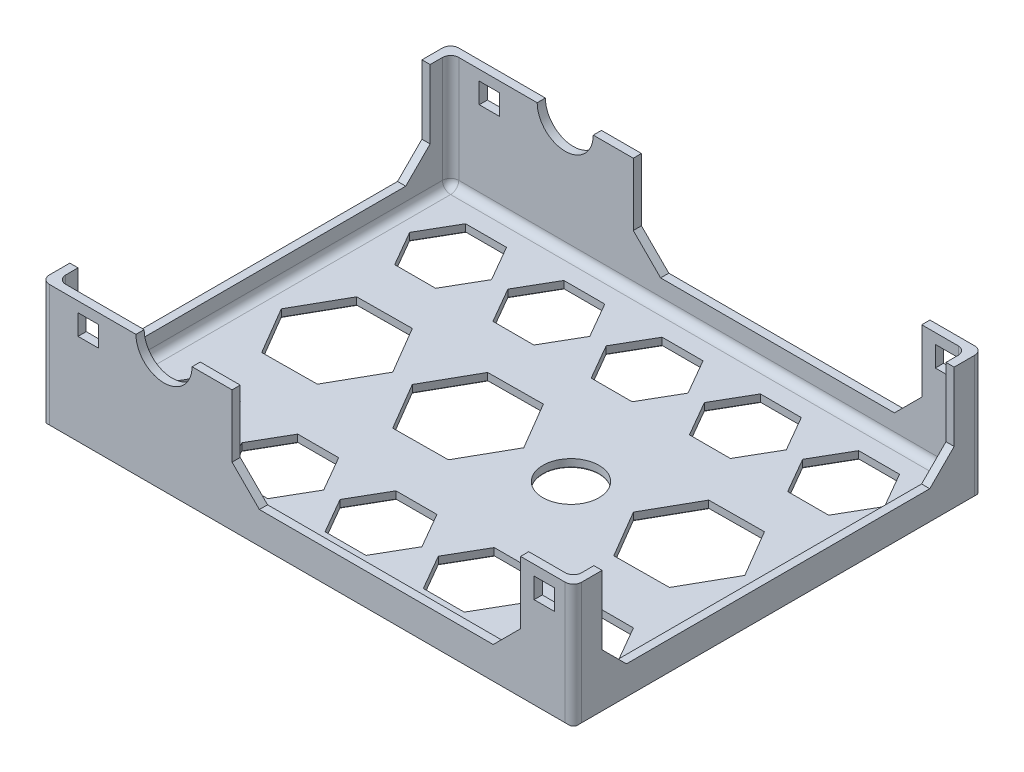
SolidWorks part; units mm, degrees
ref_plane "Front Plane" through (0, 0, 0) normal (0, 0, 1) x (1, 0, 0)
ref_plane "Top Plane" through (0, 0, 0) normal (0, 1, 0) x (1, 0, 0)
ref_plane "Right Plane" through (0, 0, 0) normal (1, 0, 0) x (0, 0, -1)
sketch "Sketch1" plane through (0, 0, 0) normal (0, 1, 0) x (1, 0, 0)
  line L1 (-65, -50) -> (65, -50)
  line L2 (-65, -50) -> (-65, 50)
  line L3 (-65, 50) -> (65, 50)
  line L4 (65, -50) -> (65, 50)
  line L5 (-65, -50) -> (65, 50) construction
  line L6 (-65, 50) -> (65, -50) construction
  point P0 (0, 0)
  dimension "D1" = 130
  dimension "D2" = 100
extrude "Boss-Extrude1" add sketch "Sketch1" along normal blind 30
shell "Shell1" thickness 2 removed face at (0, 30, 0)
chamfer "Chamfer1" distance 0.25 angle 45 4 edges at (0, 0, -50) (-65, 0, 0) (65, 0, 0) (0, 0, 50)
sketch "Sketch2" plane through (0, 0, -50) normal (0, 0, -1) x (-1, 0, 0)
  line L0 (-65, 30) -> (65, 30) construction
  line L1 (65, 30) -> (65, 0.25) construction
  circle A0 centre (35, 30) radius 6.85
  dimension "D1" = 13.7
  dimension "D2" = 30
extrude "Cut-Extrude1" cut sketch "Sketch2" against normal through all
sketch "Sketch3" plane through (0, 2, 0) normal (0, 1, 0) x (1, 0, 0)
  line L0 (-63, 48) -> (-63, -48) construction
  circle A0 centre (14.4, 0) radius 6.85
  point P4 (-63, 0)
  dimension "D1" = 13.7
  dimension "D2" = 77.4
extrude "Cut-Extrude2" cut sketch "Sketch3" against normal blind 60
sketch "Sketch5" plane through (0, 0, 50) normal (0, 0, 1) x (1, 0, 0)
  line L0 (52.09, 30) -> (52.09, 14.7)
  line L1 (-28.15, 30) -> (65, 30) construction
  line L2 (52.09, 14.7) -> (45.41, 8.02)
  line L3 (45.41, 8.02) -> (-11.7, 8.02)
  line L4 (-11.7, 8.02) -> (-18.38, 14.7)
  line L5 (-18.38, 14.7) -> (-18.38, 30)
  line L6 (-18.38, 30) -> (52.09, 30)
  line L7 (65, 30) -> (65, 0.25) construction
  line L8 (-65, 0.25) -> (65, 0.25) construction
  dimension "D1" = 7.77
  dimension "D2" = 12.91
  dimension "D3" = 135
  dimension "D4" = 135
  dimension "D5" = 57.11
  dimension "D6" = 70.47
extrude "Cut-Extrude3" cut sketch "Sketch5" against normal through all
sketch "Sketch6" plane through (65, 0, 0) normal (1, 0, 0) x (0, 0, -1)
  line L0 (-43, 30) -> (-43, 13.2056)
  line L1 (-50, 30) -> (50, 30) construction
  line L2 (-43, 13.2056) -> (-37.0444, 7.25)
  line L3 (-37.0444, 7.25) -> (37.0444, 7.25)
  line L4 (37.0444, 7.25) -> (43, 13.2056)
  line L5 (43, 13.2056) -> (43, 30)
  line L6 (43, 30) -> (-43, 30)
  line L7 (50, 30) -> (50, 0.25) construction
  line L8 (-50, 30) -> (-50, 0.25) construction
  line L9 (-50, 0.25) -> (50, 0.25) construction
  dimension "D1" = 7
  dimension "D2" = 7
  dimension "D3" = 7
  dimension "D4" = 225
  dimension "D5" = 135
extrude "Cut-Extrude4" cut sketch "Sketch6" against normal through all
sketch "Sketch7" plane through (0, 2, 0) normal (0, 1, 0) x (1, 0, 0)
  line L1 (-43, 24.3397) -> (-38, 33)
  line L2 (-38, 33) -> (-43, 41.6603)
  line L3 (-43, 41.6603) -> (-53, 41.6603)
  line L4 (-53, 41.6603) -> (-58, 33)
  line L5 (-58, 33) -> (-53, 24.3397)
  line L6 (-53, 24.3397) -> (-43, 24.3397)
  line L9 (63, 48) -> (-63, 48) construction
  line L11 (-63, 48) -> (-63, -48) construction
  circle A0 centre (-48, 33) radius 8.6603 construction
  dimension "D1" = 10
  dimension "D2" = 15
  dimension "D3" = 15
extrude "Cut-Extrude5" cut sketch "Sketch7" against normal through all
pattern_linear "LPattern1" count 5 spacing 24 along (1, 0, 0) count 2 spacing 65 along (0, 0, 1) of "Cut-Extrude5"
sketch "Sketch8" plane through (0, 2, 0) normal (0, 1, 0) x (1, 0, 0)
  line L0 (-63, -37.0444) -> (-63, 37.0444) construction
  line L1 (-37.3443, 13.0062) -> (-50.8439, 12.8975)
  line L2 (-50.8439, 12.8975) -> (-57.4996, 1.1522)
  line L3 (-57.4996, 1.1522) -> (-50.6557, -10.4844)
  line L4 (-50.6557, -10.4844) -> (-37.1561, -10.3757)
  line L5 (-37.1561, -10.3757) -> (-30.5004, 1.3696)
  line L6 (-30.5004, 1.3696) -> (-37.3443, 13.0062)
  circle A0 centre (-44, 1.2609) radius 11.6913 construction
  dimension "D1" = 27
  dimension "D2" = 19
extrude "Cut-Extrude6" cut sketch "Sketch8" against normal through all
pattern_linear "LPattern2" count 2 spacing 32 along (1, 0, 0) of "Cut-Extrude6"
pattern_linear "LPattern3" count 2 spacing 86 along (1, 0, 0) of "Cut-Extrude6"
fillet "Fillet1" radius 2 12 edges at (-63, 16, 48) (63, 16, 48) (63, 16, -48) (-63, 16, -48) (-65, 15.125, -50) (65, 15.125, -50) (65, 15.125, 50) (-65, 15.125, 50) (0, 2, 48) (-63, 2, 0) (63, 2, 0) (0, 2, -48)
chamfer "Chamfer2" distance 0.25 angle 45 78 edges at (42.0941, 0, 10.4301) (52.1717, 0, 4.5031) (52.0776, 0, -7.1879) (41.9059, 0, -12.9518) (31.8283, 0, -7.0249) (31.9224, 0, 4.6661) (48, 0, -24.3397) (55.5, 0, -28.6699) (55.5, 0, -37.3301) (48, 0, -41.6603) (40.5, 0, -37.3301) (40.5, 0, -28.6699) (31.5, 0, -28.6699) (31.5, 0, -37.3301) (24, 0, -41.6603) (16.5, 0, -37.3301) (16.5, 0, -28.6699) (24, 0, -24.3397) (40.5, 0, 27.6699) (48, 0, 23.3397) (55.5, 0, 27.6699) (55.5, 0, 36.3301) (48, 0, 40.6603) (40.5, 0, 36.3301) (31.5, 0, 27.6699) (24, 0, 23.3397) (31.5, 0, 36.3301) (24, 0, 40.6603) (16.5, 0, 36.3301) (16.5, 0, 27.6699) (-7.5, 0, 27.6699) (-7.5, 0, 36.3301) (0, 0, 40.6603) (7.5, 0, 36.3301) (7.5, 0, 27.6699) (0, 0, 23.3397) (0, 0, -41.6603) (-7.5, 0, -37.3301) (7.5, 0, -37.3301) (7.5, 0, -28.6699) (0, 0, -24.3397) (-7.5, 0, -28.6699) (-31.5, 0, -37.3301) (-24, 0, -41.6603) (-16.5, 0, -37.3301) (-16.5, 0, -28.6699) (-24, 0, -24.3397) (-31.5, 0, -28.6699) (-12.0941, 0, -12.9518) (-1.9224, 0, -7.1879) (-1.8283, 0, 4.5031) (-11.9059, 0, 10.4301) (-22.0776, 0, 4.6661) (-22.1717, 0, -7.0249) (-31.5, 0, 27.6699) (-24, 0, 23.3397) (-16.5, 0, 27.6699) (-16.5, 0, 36.3301) (-24, 0, 40.6603) (-31.5, 0, 36.3301) (-48, 0, 40.6603) (-40.5, 0, 36.3301) (-40.5, 0, 27.6699) (-48, 0, 23.3397) (-55.5, 0, 27.6699) (-55.5, 0, 36.3301) (-54.1717, 0, -7.0249) (-54.0776, 0, 4.6661) (-43.9059, 0, 10.4301) (-33.8283, 0, 4.5031) (-33.9224, 0, -7.1879) (-44.0941, 0, -12.9518) (-55.5, 0, -28.6699) (-48, 0, -24.3397) (-40.5, 0, -28.6699) (-40.5, 0, -37.3301) (-55.5, 0, -37.3301) (-48, 0, -41.6603)
fillet "Fillet2" radius 0.25 1 edges at (14.4, 0, -6.85)
sketch "Sketch9" plane through (0, 0, 50) normal (0, 0, 1) x (1, 0, 0)
  line L0 (-63, 30) -> (-41.85, 30) construction
  line L1 (-56, 27.5) -> (-51, 27.5)
  line L2 (-56, 27.5) -> (-56, 22.5)
  line L3 (-56, 22.5) -> (-51, 22.5)
  line L4 (-51, 27.5) -> (-51, 22.5)
  line L5 (-63, 30) -> (-63, 0.25) construction
  dimension "D1" = 2.5
  dimension "D2" = 7
  dimension "D3" = 5
  dimension "D4" = 5
extrude "Cut-Extrude7" cut sketch "Sketch9" against normal through all
sketch "Sketch10" plane through (0, 0, 50) normal (0, 0, 1) x (1, 0, 0)
  line L0 (63, 0.25) -> (63, 30) construction
  line L1 (55.4, 27.5) -> (60.4, 27.5)
  line L2 (55.4, 27.5) -> (55.4, 22.5)
  line L3 (55.4, 22.5) -> (60.4, 22.5)
  line L4 (60.4, 27.5) -> (60.4, 22.5)
  line L5 (-51, 27.5) -> (-56, 27.5) construction
  dimension "D1" = 5
  dimension "D2" = 2.6
  dimension "D3" = 5
extrude "Cut-Extrude8" cut sketch "Sketch10" against normal through all
